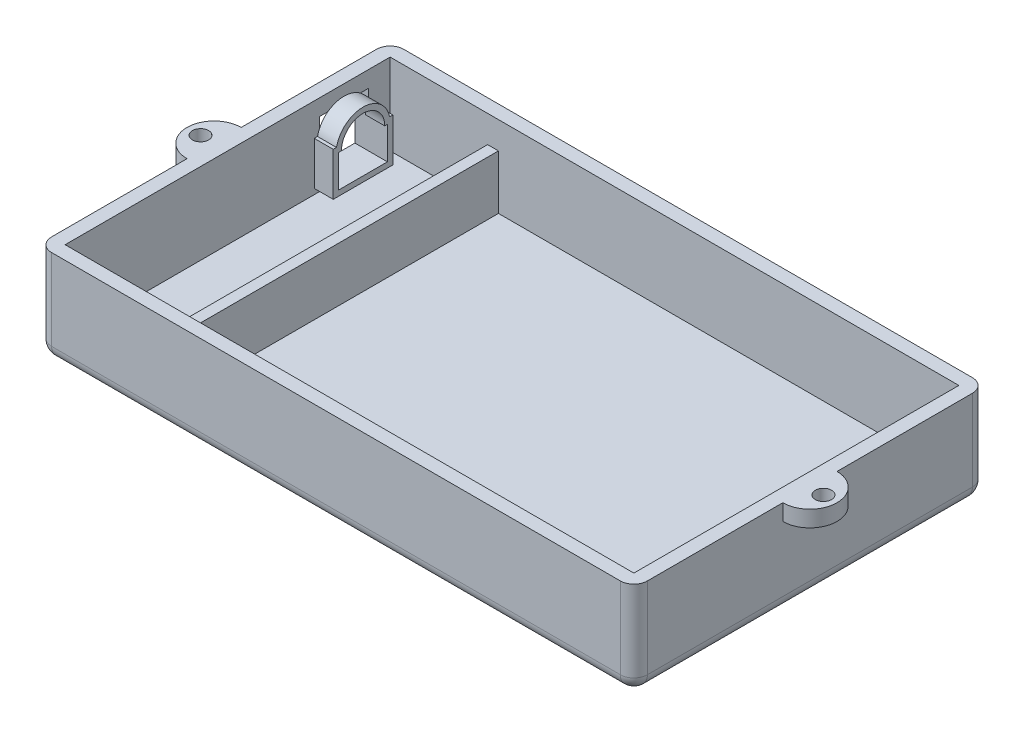
SolidWorks part; units mm, degrees
ref_plane "Front Plane" through (0, 0, 0) normal (0, 0, 1) x (1, 0, 0)
ref_plane "Top Plane" through (0, 0, 0) normal (0, 1, 0) x (1, 0, 0)
ref_plane "Right Plane" through (0, 0, 0) normal (1, 0, 0) x (0, 0, -1)
sketch "Sketch1" plane through (0, 0, 0) normal (0, 1, 0) x (1, 0, 0)
  line L1 (52.5, -30) -> (-52.5, -30)
  line L2 (52.5, -30) -> (52.5, 30)
  line L3 (52.5, 30) -> (-52.5, 30)
  line L4 (-52.5, -30) -> (-52.5, 30)
  line L5 (52.5, -30) -> (-52.5, 30) construction
  line L6 (52.5, 30) -> (-52.5, -30) construction
  point P0 (0, 0)
  dimension "D1" = 105
  dimension "D2" = 60
extrude "Boss-Extrude1" add sketch "Sketch1" along normal blind 15
shell "Shell1" thickness 2.5 removed face at (0, 15, 0) outward yes
fillet "Fillet1" radius 2.5 8 edges at (0, -2.5, 32.5) (55, 6.25, 32.5) (-55, 6.25, 32.5) (0, -2.5, -32.5) (-55, 6.25, -32.5) (55, 6.25, -32.5) (55, -2.5, 0) (-55, -2.5, 0)
sketch "Sketch3" plane through (0, 15, 0) normal (0, 1, 0) x (1, 0, 0)
  line L0 (0, 32.5) -> (0, -32.5) construction
  line L1 (-55, 30) -> (-55, -30) construction
  line L2 (52.5, 32.5) -> (-52.5, 32.5) construction
  line L3 (-52.5, -32.5) -> (52.5, -32.5) construction
  line L5 (0, 0) -> (55, 0) construction
  line L6 (55, -30) -> (55, 30) construction
  line L7 (0, 0) -> (-55, 0) construction
  line L8 (-52.5, -30) -> (52.5, -30) construction
  arc A0 (-55, -5) -> (-55, 5) centre (-55, 0) cw
  circle A2 centre (-57.5, 0) radius 1.5
  circle A3 centre (57.5, 0) radius 1.5
  arc A4 (55, -5) -> (55, 5) centre (55, 0) ccw
  point P26 (-60, 0)
  line M7 (55, -30) -> (55, 30)
  line M11 (-55, 30) -> (-55, -30)
  dimension "D1" = 5
  dimension "D2" = 30
  dimension "D3" = 3
  dimension "D4" = 2.5
  dimension "D5" = 2.5
extrude "Boss-Extrude2" add sketch "Sketch3" against normal blind 3 contours A4 A3 M7 | A0 A2 M11 region at (-59.8882, 15, 0) region at (55.1118, 15, 0)
sketch "Sketch4" plane through (0, 0, 0) normal (0, 1, 0) x (1, 0, 0)
  line L0 (52.5, -30) -> (52.5, 30) construction
  line L1 (-34.5, 30) -> (-32.5, 30)
  line L2 (-34.5, 30) -> (-34.5, -30)
  line L3 (-34.5, -30) -> (-32.5, -30)
  line L4 (-32.5, 30) -> (-32.5, -30)
  line L5 (52.5, 30) -> (-52.5, 30) construction
  point P6 (52.5, 0)
  dimension "D1" = 85
  dimension "D2" = 2
  dimension "D3" = 60
extrude "Boss-Extrude3" add sketch "Sketch4" along normal blind 10
sketch "Sketch5" plane through (-55, 0, 0) normal (-1, 0, 0) x (0, 0, 1)
  line L0 (-30, 15) -> (-30, 0) construction
  line L1 (-17.5, 8) -> (-17, 8)
  line L2 (-26, 8) -> (-26, 2)
  line L3 (-26, 2) -> (-17, 2)
  line L4 (-17, 8) -> (-17, 2)
  line L5 (-30, 0) -> (30, 0) construction
  line L6 (-21.5, 2) -> (-21.5, 12) construction
  line L7 (-25.5, 8) -> (-26, 8)
  line L8 (-27, 9) -> (-27, 1)
  line L9 (-27, 1) -> (-16, 1)
  line L10 (-16, 9) -> (-16, 1)
  line L11 (-16.601, 9) -> (-16, 9)
  line L12 (-26.399, 9) -> (-27, 9)
  arc A0 (-25.5, 8) -> (-17.5, 8) centre (-21.5, 8) cw
  arc A1 (-26.399, 9) -> (-16.601, 9) centre (-21.5, 8) cw
  point P10 (-25.5, 8)
  point P11 (-17.5, 8)
  dimension "D1" = 9
  dimension "D2" = 6
  dimension "D3" = 4
  dimension "D4" = 2
  dimension "D5" = 10
  dimension "D6" = 0.5
  dimension "D7" = 0.5
  dimension "D8" = 1
extrude "Boss-Extrude4" add sketch "Sketch5" against normal blind 6
sketch "Sketch7" plane through (-55, 0, 0) normal (-1, 0, 0) x (0, 0, 1)
  line L0 (-30, 15) -> (-30, 0) construction
  line L1 (-26, 12) -> (-17, 12)
  line L2 (-26, 12) -> (-26, 2)
  line L3 (-26, 2) -> (-17, 2)
  line L4 (-17, 12) -> (-17, 2)
  line L5 (-30, 0) -> (30, 0) construction
  dimension "D1" = 9
  dimension "D2" = 10
  dimension "D3" = 4
  dimension "D4" = 2
extrude "Cut-Extrude1" cut sketch "Sketch7" against normal blind 2.5
